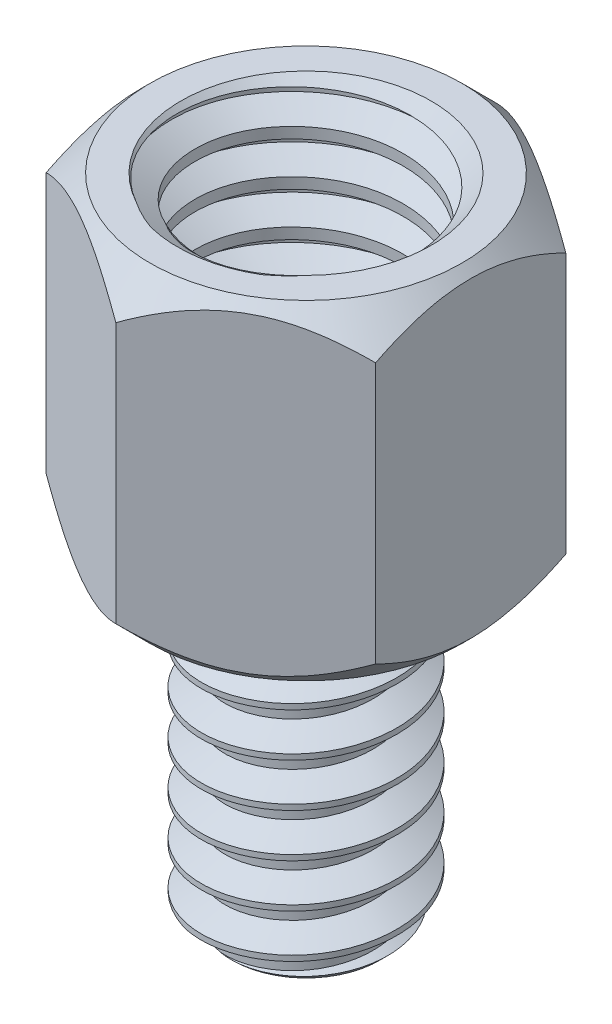
SolidWorks part; units mm, degrees
material "AISI Тип 316L нержавеющая сталь"
ref_plane "Спереди" through (0, 0, 0) normal (0, 0, 1) x (1, 0, 0)
ref_plane "Сверху" through (0, 0, 0) normal (0, 1, 0) x (1, 0, 0)
ref_plane "Справа" through (0, 0, 0) normal (1, 0, 0) x (0, 0, -1)
sketch "Эскиз1" plane through (0, 0, 0) normal (0, 1, 0) x (1, 0, 0)
  line L1 (-2.4, 1.3856) -> (-2.4, -1.3856)
  line L2 (-2.4, -1.3856) -> (0, -2.7713)
  line L3 (0, -2.7713) -> (2.4, -1.3856)
  line L4 (2.4, -1.3856) -> (2.4, 1.3856)
  line L5 (2.4, 1.3856) -> (0, 2.7713)
  line L6 (0, 2.7713) -> (-2.4, 1.3856)
  circle A0 centre (0, 0) radius 2.4 construction
  dimension "D1" = 4.8
extrude "Бобышка-Вытянуть1" add sketch "Эскиз1" along normal blind 4.8
sketch "Эскиз2" plane through (0, 0, 0) normal (1, 0, 0) x (0, 0, -1)
  line L0 (0, 0) -> (0, -4.6)
  line L1 (0, -4.6) -> (1.07, -4.6)
  line L2 (1.07, -4.6) -> (1.4224, -4.2476)
  line L3 (1.4224, -4.2476) -> (1.4224, -0.6643)
  line L4 (1.4224, -0.6643) -> (1.07, -0.5)
  line L5 (1.07, -0.5) -> (1.07, 0)
  line L6 (1.3856, 0) -> (2.7713, 0) construction
  line L7 (1.07, 0) -> (0, 0)
  line L8 (1.07, -0.5) -> (1.07, -5.0022) construction
  line L9 (-1.3856, 0) -> (1.3856, 0) construction
  dimension "D1" = 1.4224
  dimension "D2" = 1.07
  dimension "D3" = 4.6
  dimension "D4" = 0.5
  dimension "D5" = 135
  dimension "D6" = 115
revolve "Повернуть2" add sketch "Эскиз2" angle 360 about L0
sketch "Эскиз3" plane through (0, 0, 0) normal (1, 0, 0) x (0, 0, -1)
  line L0 (-2.7713, 4.8) -> (-2.7713, 4.3)
  line L1 (-2.7713, 4.8) -> (-2.7713, 0) construction
  line L2 (-2.7713, 4.3) -> (-2.2713, 4.8)
  line L4 (-2.2713, 4.8) -> (-2.7713, 4.8)
  line L5 (-2.7713, 0) -> (-2.7713, 0.5)
  line L6 (-2.7713, 0.5) -> (-2.2713, 0)
  line L7 (-2.7713, 0) -> (-1.3856, 0) construction
  line L8 (-2.2713, 0) -> (-2.7713, 0)
  dimension "D1" = 0.5
  dimension "D2" = 0.5
  dimension "D3" = 0.5
  dimension "D4" = 0.5
revolve "Вырез-Повернуть1" cut sketch "Эскиз3" angle 360 about axis through (0, 0, 0) along (0, 1, 0)
thread "Резьба1" pitch 0.635 method cut profile "Профиль резьбы1" start angle 0, offset 1, length 4.6, pitch 0.635, diameter 2.8448
ref_plane "Плоскость1" through (1.4224, -5.2476, 0) normal (0, 0, 1) x (1, 0, 0)
sketch "Профиль резьбы1" plane through (1.4224, -5.2476, 0) normal (0, 0, 1) x (1, 0, 0)
  line L0 (0, 0) -> (0, 0.635) construction
  line L11 (0, 0) -> (0, 0.5556)
  line L12 (0, 0.5556) -> (-0.3437, 0.3572)
  line L13 (-0.3437, 0.3572) -> (-0.3437, 0.1984)
  line L15 (-0.3437, 0.1984) -> (0, 0)
  line L17 (-0.3437, 0.2778) -> (0, 0.2778) construction
  point P2 (0, 0)
  dimension "Pitch" = 0.635
  dimension "Profile_Angle" = 60
  dimension "Profile_Land" = 0.1588
  dimension "Profile_Height" = 0.3437
sketch "Эскиз8" plane through (0, 4.8, 0) normal (0, 1, 0) x (1, 0, 0)
  point P0 (0, 0)
hole_wizard "Сверло под метчик  спиральное #42" positions "Трехмерный эскиз3" profile "Эскиз9" hole size "#4-40" standard "Ansi Inch"
sketch3d "Трехмерный эскиз3"
  point P0 (0, 4.8, 0)
sketch "Эскиз9" plane through (0, 4.8, 0) normal (1, 0, 0) x (0, 0, 1)
  line L0 (0, 0) -> (0, 4.4157)
  line L1 (0, 4.4157) -> (1.524, 3.5)
  line L2 (1.524, 3.5) -> (1.524, 0)
  line L5 (1.524, 0) -> (0, 0)
  line L10 (0, 4.4157) -> (-1.524, 3.5) construction
  line L11 (0, -6.35) -> (0, 107.95) construction
  dimension "Диаметр отверстия" = 3.048
  dimension "Глубина отверстия" = 3.5
  dimension "Угол заточки сверла" = 118
chamfer "Фаска1" distance 0.3 angle 45 1 edges at (0, 4.8, 1.524)
thread "Резьба2" pitch 0.635 method cut profile "Профиль резьбы2" start angle 0, offset 1, length 4, pitch 0.635, diameter 3.048
ref_plane "Плоскость2" through (-1.524, 5.5, 0) normal (0, 0, 1) x (-1, 0, 0)
sketch "Профиль резьбы2" plane through (-1.524, 5.5, 0) normal (0, 0, 1) x (-1, 0, 0)
  line L0 (0, 0) -> (0, 0.635) construction
  line L1 (0, 0) -> (0.3437, 0.1984)
  line L2 (0.3437, 0.1984) -> (0.3437, 0.2778)
  line L3 (0.3437, 0.2778) -> (0, 0.4762)
  line L4 (0.3437, 0.2381) -> (0, 0.2381) construction
  line L11 (0, 0) -> (0, 0.4762)
  point P2 (0, 0)
  dimension "Pitch" = 0.635
  dimension "Profile_Angle" = 60
  dimension "Profile_Land" = 0.0794
  dimension "Profile_Height" = 0.3437
